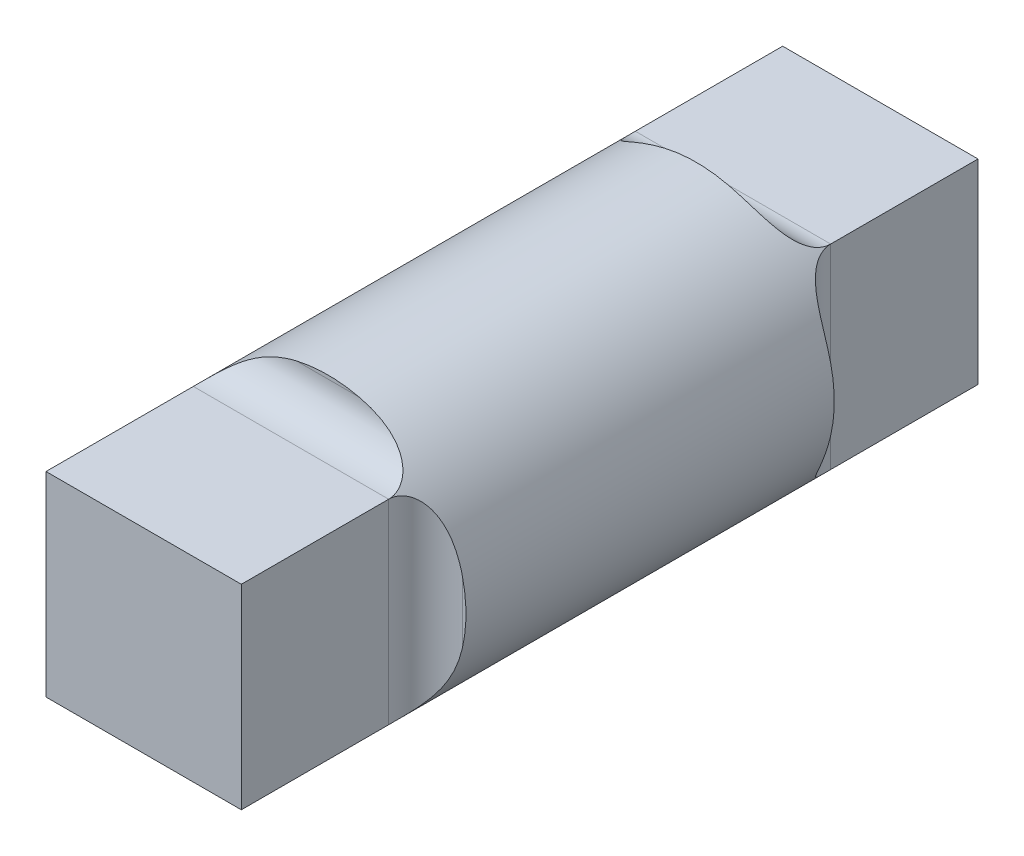
SolidWorks part; units mm, degrees
ref_plane "Front Plane" through (0, 0, 0) normal (0, 0, 1) x (1, 0, 0)
ref_plane "Top Plane" through (0, 0, 0) normal (0, 1, 0) x (1, 0, 0)
ref_plane "Right Plane" through (0, 0, 0) normal (1, 0, 0) x (0, 0, -1)
sketch "Sketch2" plane through (0, 0, 0) normal (0, 0, 1) x (1, 0, 0)
  circle A0 centre (0, 0) radius 3.75
  dimension "D1" = 7.5
extrude "Boss-Extrude1" add sketch "Sketch2" along normal blind 10
sketch "Sketch3" plane through (0, 0, 10) normal (0, 0, 1) x (1, 0, 0)
  line L1 (-2.6517, -2.6517) -> (2.6517, -2.6517)
  line L2 (-2.6517, -2.6517) -> (-2.6517, 2.6517)
  line L3 (-2.6517, 2.6517) -> (2.6517, 2.6517)
  line L4 (2.6517, -2.6517) -> (2.6517, 2.6517)
  line L5 (-2.6517, -2.6517) -> (2.6517, 2.6517) construction
  line L6 (-2.6517, 2.6517) -> (2.6517, -2.6517) construction
  circle A0 centre (0, 0) radius 3.75 construction
  point P0 (0, 0)
  dimension "D1" = 5.3033
extrude "Boss-Extrude2" add sketch "Sketch3" along normal blind 5
sketch "Sketch4" plane through (0, 0, 0) normal (0, 0, -1) x (-1, 0, 0)
  line L1 (-2.6517, -2.6517) -> (2.6517, -2.6517)
  line L2 (-2.6517, -2.6517) -> (-2.6517, 2.6517)
  line L3 (-2.6517, 2.6517) -> (2.6517, 2.6517)
  line L4 (2.6517, -2.6517) -> (2.6517, 2.6517)
  line L5 (-2.6517, -2.6517) -> (2.6517, 2.6517) construction
  line L6 (-2.6517, 2.6517) -> (2.6517, -2.6517) construction
  circle A0 centre (0, 0) radius 3.75 construction
  point P0 (0, 0)
  dimension "D1" = 5.3033
extrude "Boss-Extrude3" add sketch "Sketch4" along normal blind 5
fillet "Fillet1" radius 1 1 edges at (-2.6517, 0, 10)
fillet "Fillet3" radius 1 1 edges at (0, 2.6517, 10)
fillet "Fillet4" radius 1 1 edges at (2.6517, 0, 10)
fillet "Fillet5" radius 1 1 edges at (0, -2.6517, 10)
fillet "Fillet6" radius 1 1 edges at (0, 2.6517, 0)
fillet "Fillet7" radius 1 1 edges at (-2.6517, 0, 0)
fillet "Fillet8" radius 1 1 edges at (0, -2.6517, 0)
fillet "Fillet9" radius 1 1 edges at (2.6517, 0, 0)
